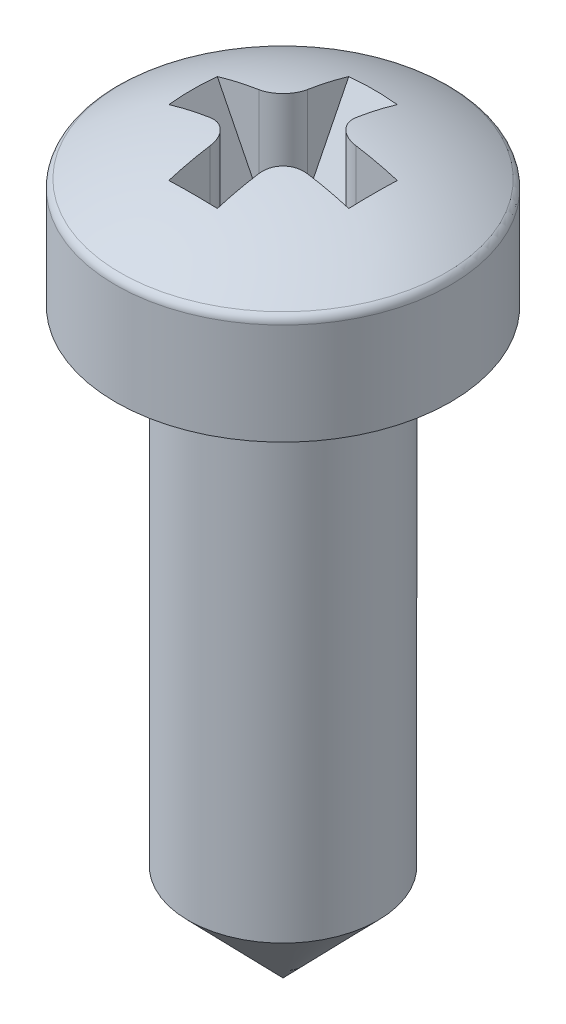
SolidWorks part; units mm, degrees
ref_plane "Front Plane" through (0, 0, 0) normal (0, 0, 1) x (1, 0, 0)
ref_plane "Top Plane" through (0, 0, 0) normal (0, 1, 0) x (1, 0, 0)
ref_plane "Right Plane" through (0, 0, 0) normal (1, 0, 0) x (0, 0, -1)
sketch "Sketch1" plane through (0, 0, 0) normal (0, 1, 0) x (1, 0, 0)
  circle A0 centre (0, 0) radius 3.45
  dimension "D1" = 6.9
extrude "Boss-Extrude1" add sketch "Sketch1" along normal blind 2.2
dome "Dome1" faces to dome 1 distance 1 reverse direction no elliptical dome no face at (0, 2.2, 3.45) parameters "D1"=1
sketch "Sketch2" plane through (0, 0, 0) normal (0, -1, 0) x (-1, 0, 0)
  circle A0 centre (0, 0) radius 1.95
  dimension "D1" = 3.9
extrude "Boss-Extrude2" add sketch "Sketch2" along normal blind 12
chamfer "Chamfer1" distance 2 distance2 1.95 1 edges at (0, -12, -1.95) first distance on face at (0, -12, -1.95)
fillet "Fillet1" radius 0.2 1 edges at (0, 2.2, 3.45)
ref_plane "Plane1" through (0, 3.2, 0) normal (0, 1, 0) x (1, 0, 0)
sketch "Sketch3" plane through (0, 3.2, 0) normal (0, 1, 0) x (1, 0, 0)
  line L0 (-2, -0.5) -> (-0.5, -0.5)
  line L1 (-0.5, -0.5) -> (-0.5, -2)
  line L2 (-0.5, -2) -> (0.5, -2)
  line L3 (0.5, -2) -> (0.5, -0.5)
  line L4 (0.5, -0.5) -> (2, -0.5)
  line L5 (2, -0.5) -> (2, 0.5)
  line L6 (2, 0.5) -> (0.5, 0.5)
  line L7 (0.5, 0.5) -> (0.5, 2)
  line L8 (0.5, 2) -> (-0.5, 2)
  line L9 (-0.5, 2) -> (-0.5, 0.5)
  line L10 (-0.5, 0.5) -> (-2, 0.5)
  line L11 (-2, 0.5) -> (-2, -0.5)
  line L12 (0.5, 0.5) -> (-0.5, -0.5) construction
  dimension "D1" = 4
  dimension "D2" = 1
extrude "Cut-Extrude1" cut sketch "Sketch3" against normal blind 2
fillet "Fillet2" radius 0.5 4 edges at (-0.5, 2.1806, 0.5) (0.5, 2.1806, 0.5) (-0.5, 2.1806, -0.5) (0.5, 2.1806, -0.5) tangent propagation no
chamfer "Chamfer2" distance 2 distance2 1 4 edges at (-2, 1.2, 0) (0, 1.2, 2) (0, 1.2, -2) (2, 1.2, 0) tangent propagation no first distance on face at (-2, 2.036, 0) first distance on face at (0, 2.036, 2) first distance on face at (0, 2.036, -2) first distance on face at (2, 2.036, 0)
